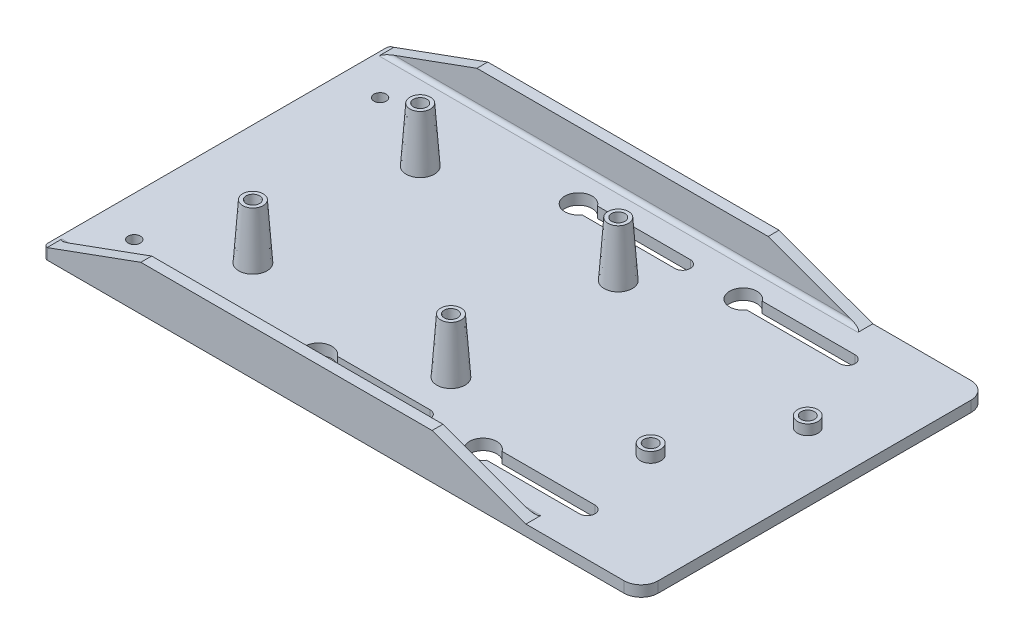
SolidWorks part; units mm, degrees
ref_plane "Front Plane" through (0, 0, 0) normal (0, 0, 1) x (1, 0, 0)
ref_plane "Top Plane" through (0, 0, 0) normal (0, 1, 0) x (1, 0, 0)
ref_plane "Right Plane" through (0, 0, 0) normal (1, 0, 0) x (0, 0, -1)
sketch "Sketch1" plane through (0, 0, 0) normal (0, 1, 0) x (1, 0, 0)
  line L0 (0, 0) -> (175, 0) construction
  line L1 (0, 50.8) -> (175, 50.8)
  line L2 (0, 50.8) -> (0, -50.8)
  line L3 (0, -50.8) -> (175, -50.8)
  line L4 (175, 50.8) -> (175, -50.8)
  line L5 (0, 50.8) -> (175, -50.8) construction
  line L6 (0, -50.8) -> (175, 50.8) construction
  point P0 (11.3289, 32.4526)
  point P5 (0, 0)
  dimension "D1" = 101.6
  dimension "D2" = 175
extrude "plate" add sketch "Sketch1" along normal blind 3.175
sketch "Sketch14" plane through (0, 0, 0) normal (0, -1, 0) x (1, 0, 0)
  text T0 "BOTTOM" font "Century Gothic" height 3.5
extrude "bottom label" cut sketch "Sketch14" against normal blind 0.6
hole_wizard "mount slots" positions "Sketch8" profile "Sketch9" size "M4" standard "ISO" slot yes end condition through all
sketch "Sketch8" plane through (0, 3.175, 0) normal (0, 1, 0) x (1, 0, 0)
  line L0 (83, 38.1) -> (131.26, 38.1) construction
  line L2 (0, 0) -> (175, 0) construction
  line L3 (175, -50.8) -> (175, 50.8) construction
  line L4 (0, 50.8) -> (0, -50.8) construction
  line L5 (83, -38.1) -> (131.26, -38.1) construction
  line L6 (65.5, 38.1) -> (100.5, 38.1) construction
  point P1 (83, 38.1)
  point P2 (131.26, 38.1)
  point P23 (131.26, -38.1)
  point P24 (83, -38.1)
  dimension "D1" = 48.26
  dimension "D2" = 38.1
  dimension "D3" = 83
  dimension "D4" = 35
sketch "Sketch9" plane through (83, 3.175, -38.1) normal (1, 0, 0) x (0, 0, 1)
  line L0 (0, 0) -> (0, 3.175)
  line L1 (0, 3.175) -> (2.25, 3.175)
  line L2 (2.25, 3.175) -> (2.25, 0)
  line L5 (2.25, 0) -> (0, 0)
  line L11 (0, -6.35) -> (0, 107.95) construction
  dimension "Thru Hole Dia." = 4.5
  dimension "Thru Hole Depth" = 3.175
sketch "Sketch12" plane through (0, 3.175, 0) normal (0, 1, 0) x (1, 0, 0)
  line L0 (-1.7462, 0) -> (1.7462, 0) construction
  circle A0 centre (116.01, 38.1) radius 4
  circle A1 centre (67.75, 38.1) radius 4
  circle A5 centre (67.75, -38.1) radius 4
  circle A6 centre (116.01, -38.1) radius 4
  arc A7 (67.75, 40.35) -> (67.75, 35.85) centre (67.75, 38.1) ccw construction
  arc A8 (116.01, 40.35) -> (116.01, 35.85) centre (116.01, 38.1) ccw construction
  dimension "D1" = 8
  dimension "D2" = 8
extrude "slot_clearance" cut sketch "Sketch12" against normal through all
hole_wizard "bracket  holes" positions "Sketch10" profile "Sketch11" hole size "M3" standard "ISO" end condition through all
sketch "Sketch10" plane through (0, 3.175, 0) normal (0, 1, 0) x (1, 0, 0)
  line L0 (0, 0) -> (175, 0) construction
  line L1 (0, 50.8) -> (0, -50.8) construction
  line L2 (175, -50.8) -> (175, 50.8) construction
  point P0 (11.75, 36)
  point P14 (11.75, -36)
  dimension "D1" = 11.75
  dimension "D2" = 36
sketch "Sketch11" plane through (11.75, 3.175, -36) normal (1, 0, 0) x (0, 0, 1)
  line L0 (0, 0) -> (0, 3.175)
  line L1 (0, 3.175) -> (1.8, 3.175)
  line L2 (1.8, 3.175) -> (1.8, 0)
  line L5 (1.8, 0) -> (0, 0)
  line L11 (0, -6.35) -> (0, 107.95) construction
  dimension "Thru Hole Dia." = 3.6
  dimension "Thru Hole Depth" = 3.175
sketch "Sketch13" plane through (0, 0, -50.8) normal (0, 0, -1) x (-1, 0, 0)
  line L0 (-141.26, 3.175) -> (-113.7852, 13.175)
  line L1 (-175, 3.175) -> (0, 3.175) construction
  line L2 (-113.7852, 13.175) -> (-28.4748, 13.175)
  line L3 (-28.4748, 13.175) -> (-1, 3.175)
  line L4 (-1, 3.175) -> (-141.26, 3.175)
  line L6 (0, 3.175) -> (0, 0) construction
  point P10 (0, 1.5875)
  dimension "D1" = 20
  dimension "D2" = 10
  dimension "D3" = 20
  dimension "D4" = 1
  dimension "D5" = 10
extrude "plate stiffener" add sketch "Sketch13" against normal blind 3.175
mirror "stiffener mirror" about plane through (0, 0, 0) normal (0, 0, 1) of "plate stiffener"
sketch "Sketch15" plane through (0, 3.175, 0) normal (0, 1, 0) x (1, 0, 0)
  line L1 (0, 0) -> (102.1318, 0) construction
  line L2 (64, 24.5) -> (64, 0) construction
  line L3 (35, 24.5) -> (93, 24.5) construction
  line L4 (-7.2462, 0) -> (7.2462, 0) construction
  circle A1 centre (93, 24.5) radius 4.125
  circle A2 centre (35, 24.5) radius 4.125
  circle A3 centre (35, -24.5) radius 4.125
  circle A4 centre (93, -24.5) radius 4.125
  dimension "D1" = 8.25
  dimension "D4" = 58
  dimension "D2" = 35
  dimension "D3" = 24.5
extrude "pi standoffs" add sketch "Sketch15" along normal blind 16 draft 4
hole_wizard "pi hole M2.5 tapped" positions "Sketch18" profile "Sketch19" hole size "M2.5" standard "ISO" end condition through all
sketch "Sketch18" plane through (0, 19.175, 0) normal (0, 1, 0) x (1, 0, 0)
  circle A0 centre (93, -24.5) radius 3.0062 construction
  circle A1 centre (35, -24.5) radius 3.0062 construction
  circle A2 centre (35, 24.5) radius 3.0062 construction
  circle A3 centre (93, 24.5) radius 3.0062 construction
  point P0 (35, -24.5)
  point P2 (35, 24.5)
  point P4 (93, 24.5)
  point P6 (93, -24.5)
sketch "Sketch19" plane through (35, 19.175, 24.5) normal (1, 0, 0) x (0, 0, 1)
  line L0 (0, 0) -> (0, 19.175)
  line L1 (0, 19.175) -> (1.77, 19.175)
  line L2 (1.77, 19.175) -> (1.77, 2.8601)
  line L3 (1.77, 2.8601) -> (1.97, 0)
  line L5 (1.97, 0) -> (0, 0)
  line L6 (-1.77, 2.8601) -> (-1.97, 0) construction
  line L11 (0, -6.35) -> (0, 107.95) construction
  dimension "Thru Hole Dia." = 3.54
  dimension "Thru Hole Depth" = 19.175
  dimension "Near C'Sink Dia." = 3.94
  dimension "Near C'Sink Angle" = 8
sketch "Sketch20" plane through (0, 3.175, 0) normal (0, 1, 0) x (1, 0, 0)
  line L0 (0, 0) -> (175, 0) construction
  line L1 (142, -15) -> (158, -15) construction
  line L2 (142, -15) -> (142, 15) construction
  line L3 (142, 15) -> (158, 15) construction
  line L4 (158, -15) -> (158, 15) construction
  line L5 (0, 50.8) -> (0, -50.8) construction
  line L7 (175, -50.8) -> (175, 50.8) construction
  circle A0 centre (158, 15) radius 3
  circle A1 centre (142, -15) radius 3
  point P0 (158, 15)
  point P1 (142, -15)
  point P8 (142, 0)
  point P9 (158, 0)
  dimension "D4" = 6
  dimension "D5" = 6
  dimension "D1" = 16
  dimension "D2" = 30
  dimension "D3" = 142
extrude "reg standoffs" add sketch "Sketch20" along normal blind 3
hole_wizard "reg hole M2.5 tapped" positions "Sketch21" profile "Sketch22" hole size "M2.5" standard "ISO" end condition through all
sketch "Sketch21" plane through (0, 6.175, 0) normal (0, 1, 0) x (1, 0, 0)
  circle A0 centre (158, 15) radius 3 construction
  circle A1 centre (142, -15) radius 3 construction
  point P0 (142, -15)
  point P2 (158, 15)
sketch "Sketch22" plane through (142, 6.175, 15) normal (1, 0, 0) x (0, 0, 1)
  line L0 (0, 0) -> (0, 6.175)
  line L1 (0, 6.175) -> (1.77, 6.175)
  line L2 (1.77, 6.175) -> (1.77, 2.8601)
  line L3 (1.77, 2.8601) -> (1.97, 0)
  line L5 (1.97, 0) -> (0, 0)
  line L6 (-1.77, 2.8601) -> (-1.97, 0) construction
  line L11 (0, -6.35) -> (0, 107.95) construction
  dimension "Thru Hole Dia." = 3.54
  dimension "Thru Hole Depth" = 6.175
  dimension "Near C'Sink Dia." = 3.94
  dimension "Near C'Sink Angle" = 8
fillet "Fillet 1.2mm" radius 1.2 4 edges at (71.13, 3.175, 47.625) (71.13, 3.175, -47.625) (0, 1.5875, -50.8) (0, 1.5875, 50.8)
fillet "Fillet2" radius 5 2 edges at (175, 1.5875, 50.8) (175, 1.5875, -50.8)
